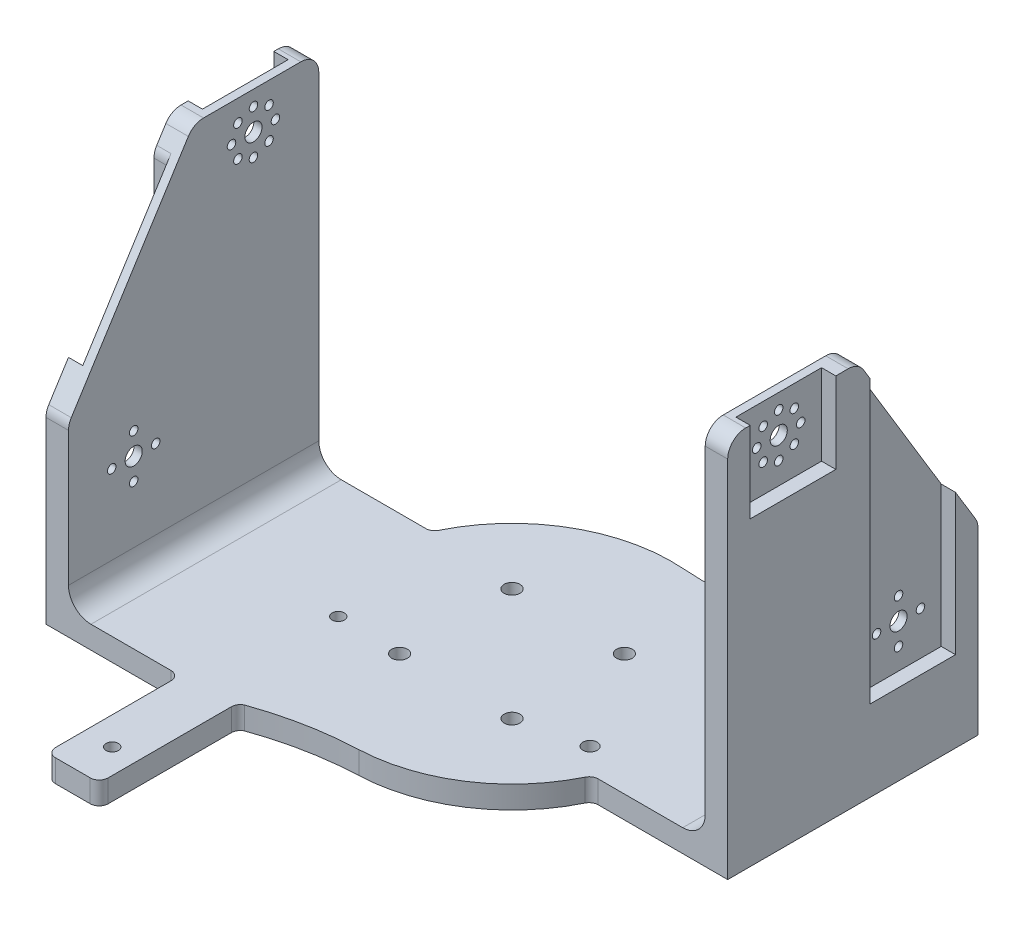
SolidWorks part; units mm, degrees
ref_plane "Front" through (0, 0, 0) normal (0, 0, 1) x (1, 0, 0)
ref_plane "Top" through (0, 0, 0) normal (0, 1, 0) x (1, 0, 0)
ref_plane "Right" through (0, 0, 0) normal (1, 0, 0) x (0, 0, -1)
sketch "Sketch2" plane through (0, 0, 0) normal (0, 1, 0) x (1, 0, 0)
  line L0 (0, 0) -> (0, -141.6255) construction
  line L1 (-115, -141.6255) -> (115, -141.6255)
  line L2 (-115, -141.6255) -> (-115, 141.6255)
  line L3 (-115, 141.6255) -> (115, 141.6255)
  line L4 (115, -141.6255) -> (115, 141.6255)
  line L5 (0, 0) -> (-115, 0) construction
  point P0 (0, 0)
  dimension "D1" = 283.251
  dimension "D2" = 230
extrude "Boss-Extrude1" add sketch "Sketch2" along normal blind 10
sketch "Sketch3" plane through (0, 0, 0) normal (0, 1, 0) x (1, 0, 0)
  line L0 (-115, -141.6255) -> (115, -141.6255) construction
  line L1 (-115, 141.6255) -> (-125, 141.6255)
  line L2 (-115, 141.6255) -> (-115, -141.6255)
  line L3 (-115, -141.6255) -> (-125, -141.6255)
  line L4 (-125, 141.6255) -> (-125, -141.6255)
  line L5 (0, 0) -> (0, 141.6255) construction
  line L6 (115, 141.6255) -> (-115, 141.6255) construction
  line L7 (125, 141.6255) -> (125, -141.6255)
  line L8 (115, -141.6255) -> (125, -141.6255)
  line L9 (115, 141.6255) -> (115, -141.6255)
  line L10 (115, 141.6255) -> (125, 141.6255)
  dimension "D1" = 10
extrude "Boss-Extrude2" add sketch "Sketch3" along normal blind 170
sketch "Sketch4" plane through (0, 10, 0) normal (0, 1, 0) x (1, 0, 0)
  point P4 (0, 0)
hole_wizard "M6 Clearance Hole1" positions "Sketch5" profile "Sketch6" hole size "M6" standard "ANSI Metric" end condition up to next
sketch "Sketch5" plane through (0, 10, 0) normal (0, 1, 0) x (1, 0, 0)
  line L0 (0, 0) -> (0, 25) construction
  line L1 (0, 25) -> (-25, 25) construction
  line L3 (0, 25) -> (25, 25) construction
  point P0 (-25, 25)
  point P13 (25, 25)
  point P14 (25, -25)
  point P15 (-25, -25)
  dimension "D1" = 25
  dimension "D2" = 4
sketch "Sketch6" plane through (-25, 10, -25) normal (1, 0, 0) x (0, 0, 1)
  line L0 (0, 0) -> (0, 10)
  line L1 (0, 10) -> (3.5, 10)
  line L2 (3.5, 10) -> (3.5, 0)
  line L5 (3.5, 0) -> (0, 0)
  line L11 (0, -6.35) -> (0, 107.95) construction
  dimension "Thru Hole Dia." = 7
  dimension "Thru Hole Depth" = 10
sketch "Sketch7" plane through (115, 0, 0) normal (-1, 0, 0) x (0, 0, 1)
  line L0 (-141.6255, 170) -> (141.6255, 170) construction
  line L1 (0, 153.49) -> (0, 163.269) construction
  line L2 (0, 153.49) -> (0, 163.269) construction
  circle A0 centre (0, 153.49) radius 3.81
  circle A1 centre (0, 163.269) radius 1.8987
  circle A2 centre (6.9148, 160.4048) radius 1.8987
  circle A3 centre (9.779, 153.49) radius 1.8987
  circle A4 centre (6.9148, 146.5752) radius 1.8987
  circle A5 centre (0, 143.711) radius 1.8987
  circle A6 centre (-6.9148, 146.5752) radius 1.8987
  circle A7 centre (-9.779, 153.49) radius 1.8987
  circle A8 centre (-6.9148, 160.4048) radius 1.8987
  point P7 (0, 170)
  dimension "D1" = 7.62
  dimension "D3" = 3.7973
  dimension "D2" = 16.51
  dimension "D6" = 9.779
  dimension "D5" = 8
extrude "Cut-Extrude1" cut sketch "Sketch7" against normal through all both and the other way through all
sketch "Sketch8" plane through (0, 170, 0) normal (0, 1, 0) x (1, 0, 0)
  line L1 (118.65, -19.05) -> (125, -19.05)
  line L2 (118.65, -19.05) -> (118.65, 19.05)
  line L3 (118.65, 19.05) -> (125, 19.05)
  line L4 (125, -19.05) -> (125, 19.05)
  line L5 (118.65, -19.05) -> (125, 19.05) construction
  line L6 (118.65, 19.05) -> (125, -19.05) construction
  line L9 (125, -141.6255) -> (125, 141.6255) construction
  line L10 (0, 0) -> (0, 141.6255) construction
  line L11 (115, 141.6255) -> (-115, 141.6255) construction
  line L13 (-118.65, 19.05) -> (-125, -19.05) construction
  line L14 (-118.65, -19.05) -> (-125, 19.05) construction
  line L16 (-125, -19.05) -> (-125, 19.05)
  line L17 (-118.65, 19.05) -> (-125, 19.05)
  line L18 (-118.65, -19.05) -> (-118.65, 19.05)
  line L19 (-118.65, -19.05) -> (-125, -19.05)
  point P0 (121.825, 0)
  point P12 (125, 0)
  point P23 (-121.825, 0)
  dimension "D1" = 38.1
  dimension "D2" = 6.35
extrude "Cut-Extrude2" cut sketch "Sketch8" against normal blind 36.025
sketch "Sketch9" plane through (125, 0, 0) normal (1, 0, 0) x (0, 0, -1)
  line L0 (36.7741, 38.486) -> (42.8701, 38.486) construction
  line L2 (72.2941, 74.514) -> (72.2941, 35.986)
  line L3 (72.2941, 35.986) -> (34.2741, 35.986)
  line L4 (34.2741, 74.514) -> (34.2741, 35.986)
  line L5 (72.2941, 74.514) -> (34.2741, 35.986) construction
  line L6 (72.2941, 35.986) -> (34.2741, 74.514) construction
  line L7 (36.7741, 47.63) -> (36.7741, 38.486) construction
  line L9 (34.2741, 74.514) -> (72.2941, 74.514) construction
  line L10 (34.2741, 74.514) -> (34.2741, 170)
  line L11 (19.05, 170) -> (141.6255, 170) construction
  line L12 (34.2741, 170) -> (72.2941, 170)
  line L13 (72.2941, 170) -> (72.2941, 74.514)
  point P0 (53.2841, 55.25)
  point P10 (53.2841, 65.029)
  point P11 (43.5051, 55.25)
  point P13 (53.2841, 45.471)
  point P15 (63.0631, 55.25)
  dimension "D1" = 2.5
  dimension "D2" = 2.5
extrude "Cut-Extrude3" cut sketch "Sketch9" against normal blind 6.35
sketch "Sketch11" plane through (118.65, 0, 0) normal (1, 0, 0) x (0, 0, -1)
  circle A0 centre (53.2841, 55.25) radius 3.81
  circle A1 centre (0, 153.49) radius 3.81 construction
extrude "Cut-Extrude4" cut sketch "Sketch11" against normal up to next
hole_wizard "#6 Clearance Hole1" positions "Sketch12" profile "Sketch13" hole size "#6" standard "ANSI Inch" end condition up to next
sketch "Sketch12" plane through (118.65, 0, 0) normal (1, 0, 0) x (0, 0, -1)
  point P0 (53.2841, 65.029)
  point P3 (43.5051, 55.25)
  point P6 (63.0631, 55.25)
  point P10 (53.2841, 45.471)
sketch "Sketch13" plane through (118.65, 65.029, -53.2841) normal (0, 1, 0) x (0, 0, -1)
  line L0 (0, 0) -> (0, 3.65)
  line L1 (0, 3.65) -> (1.8986, 3.65)
  line L2 (1.8986, 3.65) -> (1.8986, 0)
  line L5 (1.8986, 0) -> (0, 0)
  line L11 (0, -6.35) -> (0, 107.95) construction
  dimension "Thru Hole Dia." = 3.7973
  dimension "Thru Hole Depth" = 3.65
ref_plane "Plane1" through (0, 0, 0) normal (-0.7071, 0, 0.7071) x (0.7071, 0, 0.7071)
ref_axis "Axis1" through (0, 0, 0) along (0, 1, 0)
pattern_circular "CirPattern1" count 2 over 360 about axis through (0, 0, 0) along (0, 1, 0) of "Cut-Extrude3", "Cut-Extrude4", "#6 Clearance Hole1"
sketch "Esquisse1" plane through (0, 10, 0) normal (0, 1, 0) x (1, 0, 0)
  circle A0 centre (53, 82.2686) radius 3.175
  circle A1 centre (53, -18.2676) radius 3.175
  dimension "D1" = 6.35
  dimension "D2" = 6.35
extrude "Enlèv. mat.-Extru.1" cut sketch "Esquisse1" against normal up to next
sketch "Sketch17" plane through (0, 10, 0) normal (0, 1, 0) x (1, 0, 0)
  point P0 (-53, -24.2997)
  point P1 (-53, -124.8358)
hole_wizard "CBORE for M5 SHCS1" positions "Sketch18" profile "Sketch19" counterbore size "M5" standard "ANSI Metric" end condition through all
sketch "Sketch18" plane through (0, 0, 0) normal (0, -1, 0) x (-1, 0, 0)
  point P0 (53, -24.2997)
  point P3 (53, -124.8358)
sketch "Sketch19" plane through (-53, 0, 24.2997) normal (1, 0, 0) x (0, 0, -1)
  line L0 (0, 0) -> (0, 170)
  line L1 (0, 170) -> (2.75, 170)
  line L3 (2.75, 170) -> (2.75, 5)
  line L4 (2.75, 5) -> (5, 5)
  line L5 (5, 5) -> (5, 0)
  line L7 (5, 0) -> (0, 0)
  line L11 (0, -6.35) -> (0, 107.95) construction
  dimension "Thru Hole Dia." = 5.5
  dimension "Thru Hole Depth" = 170
  dimension "C'Bore Dia." = 10
  dimension "C'Bore Depth" = 5
sketch "Sketch15" plane through (0, 10, 0) normal (0, 1, 0) x (1, 0, 0)
  line L17 (115, 141.6255) -> (-115, 141.6255) construction
  line L23 (125, 141.6255) -> (-125, 141.6255)
  line L24 (-125, 141.6255) -> (-125, 29.05)
  line L25 (-125, 141.6255) -> (-125, 19.05) construction
  line L33 (-125, 29.05) -> (-64.8453, 29.05)
  line L34 (39.825, 95.4436) -> (66.175, 95.4436)
  line L36 (66.175, 95.4436) -> (66.175, 82.2941)
  line L39 (66.175, 82.2941) -> (125, 82.2941)
  line L42 (125, 82.2941) -> (125, 141.6255)
  line L45 (118.65, 72.2941) -> (125, 72.2941) construction
  line L46 (39.825, 58.8454) -> (39.825, 95.4436)
  line L48 (125, -141.6255) -> (125, -29.05)
  line L49 (125, -29.05) -> (64.8453, -29.05)
  line L52 (-66.175, -82.2941) -> (-125, -82.2941)
  line L53 (-125, -82.2941) -> (-125, -141.6255)
  line L56 (-66.175, -82.2941) -> (-66.175, -141.6255)
  line L57 (-39.825, -95.4436) -> (-66.175, -95.4436) [skipped]
  line L58 (-39.825, -58.8454) -> (-39.825, -95.4436) [skipped]
  line L59 (-66.175, -95.4436) -> (-66.175, -82.2941) [skipped]
  line L60 (-39.825, -58.8454) -> (-39.825, -141.6255)
  line L61 (-125, -141.6255) -> (125, -141.6255) [skipped]
  line L62 (-115, -141.6255) -> (115, -141.6255) construction
  line L63 (-39.825, -141.6255) -> (125, -141.6255)
  line L64 (-66.175, -141.6255) -> (-125, -141.6255)
  circle A0 centre (0, 0) radius 71.055 construction
  circle A1 centre (-53, -24.2997) radius 2.75 construction
  circle A2 centre (53, 82.2686) radius 3.175 construction
  arc A3 (-64.8453, 29.05) -> (39.825, 58.8454) centre (0, 0) cw
  arc A5 (64.8453, -29.05) -> (-39.825, -58.8454) centre (0, 0) cw
  point P34 (0, 0)
  dimension "D1" = 10
  dimension "D3" = 10
  dimension "D4" = 10
  dimension "D5" = 10
  dimension "D2" = 10
  dimension "D6" = 10
  dimension "D7" = 2
extrude "Cut-Extrude5" cut sketch "Sketch15" against normal through all both and the other way through all
sketch "Sketch20" plane through (0, 10, 0) normal (0, 1, 0) x (1, 0, 0)
  line L0 (-65.41, -82.2941) -> (-66.175, -82.2941)
  line L1 (-65.41, -113.5375) -> (-65.41, -80.0058) construction
  line L2 (-65.41, -82.2941) -> (-65.41, -141.6255)
  line L3 (-65.41, -141.6255) -> (-66.175, -141.6255)
  line L4 (-66.175, -141.6255) -> (-66.175, -82.2941)
  line L7 (-66.175, -141.6255) -> (-39.825, -141.6255) construction
  line L8 (-39.825, -141.6255) -> (-39.825, -79.278)
  line L9 (-39.825, -141.6255) -> (-39.825, -58.8454) construction
  line L10 (-41.9959, -82.8353) -> (-41.9959, -141.6255)
  line L11 (39.825, 95.4436) -> (66.175, 95.4436)
  line L13 (-41.9959, -141.6255) -> (-39.825, -141.6255)
  line L14 (66.175, 95.4436) -> (39.825, 95.4436) construction
  line L16 (39.825, 95.4436) -> (39.825, 58.8454) construction
  line L17 (39.825, 72.5537) -> (39.825, 95.4436)
  line L18 (66.175, 95.4436) -> (66.175, 82.2941)
  line L19 (66.175, 82.2941) -> (65.41, 82.2941)
  line L23 (42, 76.1131) -> (42, 88.1131)
  line L24 (46, 92.1131) -> (61.41, 92.1131)
  line L25 (65.41, 88.1131) -> (65.41, 82.2941)
  arc A2 (-37.9959, -78.8353) -> (-41.9959, -82.8353) centre (-37.9959, -82.8353) ccw construction
  arc A3 (-41.9959, -82.8353) -> (-39.825, -79.278) centre (-37.9959, -82.8353) cw
  arc A6 (42, 76.1131) -> (39.825, 72.5537) centre (38, 76.1131) cw
  arc A7 (38, 72.1131) -> (42, 76.1131) centre (38, 76.1131) ccw construction
  arc A8 (42, 88.1131) -> (46, 92.1131) centre (46, 88.1131) cw
  arc A9 (61.41, 92.1131) -> (65.41, 88.1131) centre (61.41, 88.1131) cw
extrude "Cut-Extrude7" cut sketch "Sketch20" against normal through all both and the other way through all
fillet "Fillet2" radius 4 2 edges at (-41.9959, 5, 141.6255) (-65.41, 5, 141.6255)
fillet "Fillet3" radius 144 2 edges at (39.825, 5, -58.8454) (-39.825, 5, 58.8454)
fillet "Fillet4" radius 4 4 edges at (65.41, 5, -82.2941) (-64.8453, 5, -29.05) (64.8453, 5, 29.05) (-65.41, 5, 82.2941)
sketch "Sketch22" plane through (-125, 0, 0) normal (-1, 0, 0) x (0, 0, 1)
  line L0 (26.6221, 170) -> (82.2941, 82.011)
  line L1 (19.05, 170) -> (34.2741, 170) construction
  line L2 (82.2941, 0) -> (82.2941, 170) construction
  line L3 (72.2941, 72.011) -> (82.2941, 72.011) construction
  line L4 (82.2941, 72.011) -> (82.2941, 82.011) construction
  line L5 (19.05, 170) -> (26.6221, 170) construction
  line L6 (-19.05, 170) -> (-26.6221, 170) construction
  line L7 (-82.2941, 170) -> (29.05, 170) construction
  line L8 (26.6221, 170) -> (82.2941, 170)
  line L9 (82.2941, 170) -> (82.2941, 82.011)
  line L10 (19.05, 133.975) -> (19.05, 170) construction
  line L11 (72.2941, 35.986) -> (72.2941, 72.011) construction
extrude "Cut-Extrude8" cut sketch "Sketch22" against normal up to next
sketch "Sketch23" plane through (125, 0, 0) normal (1, 0, 0) x (0, 0, -1)
  line L0 (19.05, 170) -> (29.05, 170) construction
  line L1 (19.05, 170) -> (34.2741, 170) construction
  line L2 (29.05, 170) -> (82.2941, 82.011)
  line L3 (82.2941, 0) -> (82.2941, 170) construction
  line L4 (82.2941, 82.011) -> (82.2941, 72.011) construction
  line L5 (82.2941, 72.011) -> (72.2941, 72.011) construction
  line L6 (-19.05, 170) -> (-29.05, 170) construction
  line L7 (82.2941, 82.011) -> (82.2941, 170)
  line L8 (82.2941, 170) -> (29.05, 170)
  line L9 (72.2941, 35.986) -> (72.2941, 72.011) construction
  line L10 (19.05, 133.975) -> (19.05, 170) construction
extrude "Cut-Extrude9" cut sketch "Sketch23" against normal up to next
fillet "Fillet5" radius 8 6 edges at (120, 82.011, -82.2941) (120, 170, -29.05) (-120, 170, -29.05) (120, 170, 29.05) (-120, 170, 26.6221) (-120, 82.011, 82.2941)
split "Split1" [suppressed] bodies to split 136
fillet "Fillet6" radius 8 1 edges at (-121.825, 157.906, 34.2741)
fillet "Fillet7" radius 10 2 edges at (115, 10, -26.6221) (-115, 10, 26.6221)
equation "\"Longueur\"= 230"
equation "\"D2@Sketch2\"=\"Longueur\""
equation "\"Largeur\"= 280 + 2 * 1.6255mm"
equation "\"D1@Sketch2\"=\"Largeur\""
equation "\"D1@Sketch9\"=\"D2@Sketch9\""
